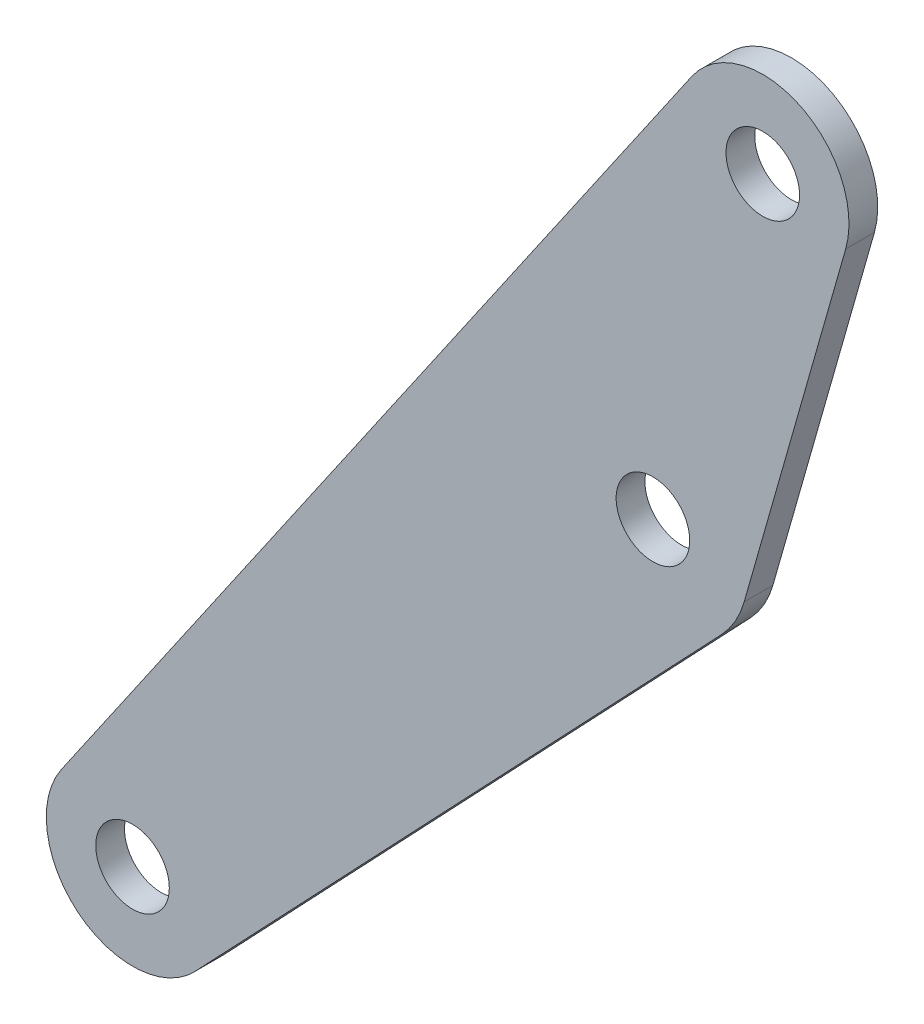
SolidWorks part; units mm, degrees
ref_plane "Front Plane" through (0, 0, 0) normal (0, 0, 1) x (1, 0, 0)
ref_plane "Top Plane" through (0, 0, 0) normal (0, 1, 0) x (1, 0, 0)
ref_plane "Right Plane" through (0, 0, 0) normal (1, 0, 0) x (0, 0, -1)
sketch "Sketch1" plane through (0, 0, 0) normal (0, 0, 1) x (1, 0, 0)
  line L1 (5.0382, -1.4355) -> (10.648, 18.2536)
  line L7 (3.8006, -3.6055) -> (-25.2925, -34.2725)
  line L8 (-32.6699, -28.2934) -> (2.1454, 22.2598)
  circle A7 centre (0, 0) radius 2.032
  circle A9 centre (6.0677, 19.5585) radius 2.032
  arc A12 (10.648, 18.2536) -> (2.1454, 22.2598) centre (6.0677, 19.5585) ccw
  arc A13 (3.8006, -3.6055) -> (5.0382, -1.4355) centre (0, 0) ccw
  circle A14 centre (-28.7476, -30.9947) radius 2.032
  arc A15 (-32.6699, -28.2934) -> (-25.2925, -34.2725) centre (-28.7476, -30.9947) ccw
  circle A16 centre (-28.7476, -30.9947) radius 2.032 construction
  circle A18 centre (6.0677, 19.5585) radius 2.032 construction
  point P5 (-27.1383, 0)
  point P6 (7.826, -21.6908)
  point P17 (-23.5143, 0)
  point P18 (-25.7656, 0)
  point P19 (-24.4584, 0)
  point P20 (-21.8684, -1.2662)
  dimension "D1" = 4.7625
  dimension "D2" = 4.064
  dimension "D3" = 10.4775
extrude "Boss-Extrude1" add sketch "Sketch1" along normal blind 1.5875
